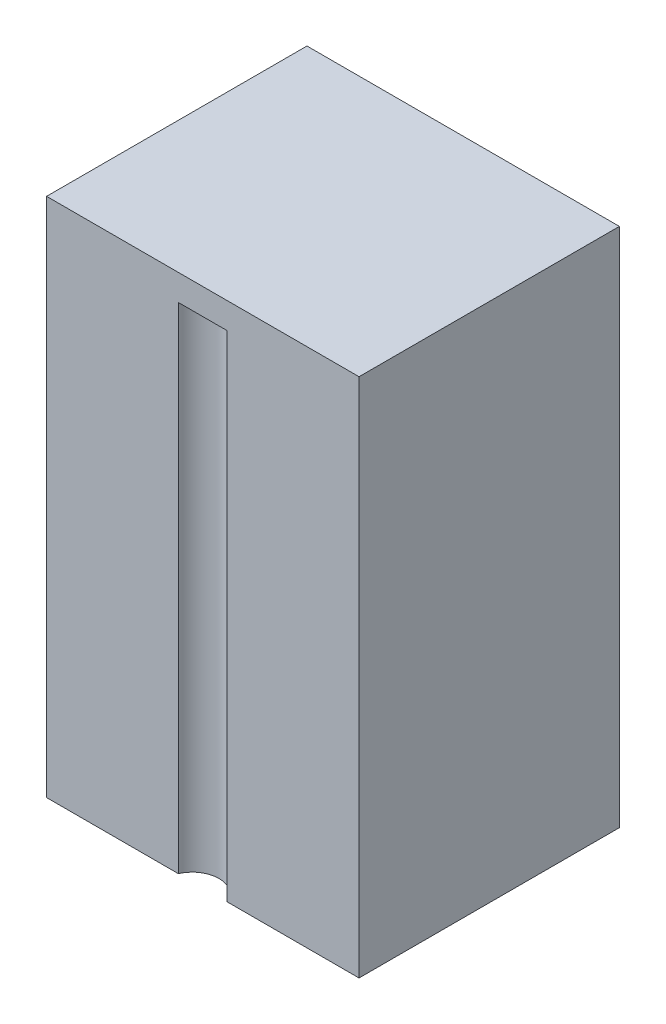
SolidWorks part; units mm, degrees
material "1060 Alloy"
ref_plane "Front Plane" through (0, 0, 0) normal (0, 0, 1) x (1, 0, 0)
ref_plane "Top Plane" through (0, 0, 0) normal (0, 1, 0) x (1, 0, 0)
ref_plane "Right Plane" through (0, 0, 0) normal (1, 0, 0) x (0, 0, -1)
sketch "Sketch1" plane through (0, 0, 0) normal (0, 1, 0) x (1, 0, 0)
  line L0 (-12.5, 10) -> (12.5, 10)
  line L1 (-15, -12.5) -> (15, -12.5)
  line L2 (-15, -12.5) -> (-15, 12.5)
  line L3 (-15, 12.5) -> (15, 12.5)
  line L4 (15, -12.5) -> (15, 12.5)
  line L5 (-15, -12.5) -> (15, 12.5) construction
  line L6 (-15, 12.5) -> (15, -12.5) construction
  line L7 (12.5, -10) -> (12.5, 10)
  line L8 (-12.5, -10) -> (12.5, -10)
  line L9 (-12.5, -10) -> (-12.5, 10)
  point P0 (0, 0)
  dimension "D1" = 30
  dimension "D2" = 25
  dimension "D3" = 2.5
extrude "Boss-Extrude1" add sketch "Sketch1" along normal blind 50 contours L1 L4 L3 L2
extrude "Cut-Extrude2" cut sketch "Sketch1<5>" along normal blind 45 from offset 2.5 contours L9 L8 L7 L0 region at (0, 0, 0)
sketch "Sketch1<5>" plane through (0, 0, 0) normal (0, 1, 0) x (1, 0, 0) same geometry as "Sketch1"
extrude "Boss-Extrude3" add sketch "Sketch1<6>" along normal blind 1 from offset 25 contours L9 L8 L7 L0 region at (0, 0, 0)
sketch "Sketch1<6>" plane through (0, 0, 0) normal (0, 1, 0) x (1, 0, 0) same geometry as "Sketch1"
sketch "Sketch2" plane through (0, 47.5, 0) normal (0, -1, 0) x (-1, 0, 0)
  line L0 (12.5, -10) -> (-12.5, -10) construction
  circle A0 centre (0, -13.5) radius 2.55
  dimension "D1" = 5.1
  dimension "D2" = 3.5
extrude "Cut-Extrude3" cut sketch "Sketch2" against normal up to surface (-47.5 mm away) contours A0 up to face at (0, 0, 0)
sketch "Sketch4" plane through (0, 26, 0) normal (0, 1, 0) x (1, 0, 0)
  line L0 (-12.5, -10) -> (12.5, -10)
  line L1 (-12.5, -10) -> (12.5, -10) construction
  line L2 (-12.5, -10) -> (-12.5, 10) construction
  line L3 (12.5, -10) -> (12.5, -5)
  line L4 (12.5, -10) -> (12.5, 10) construction
  line L5 (12.5, -5) -> (-12.5, -5)
  line L6 (-12.5, -5) -> (-12.5, -10)
  dimension "D1" = 5
extrude "Cut-Extrude4" cut sketch "Sketch4" against normal blind 1
